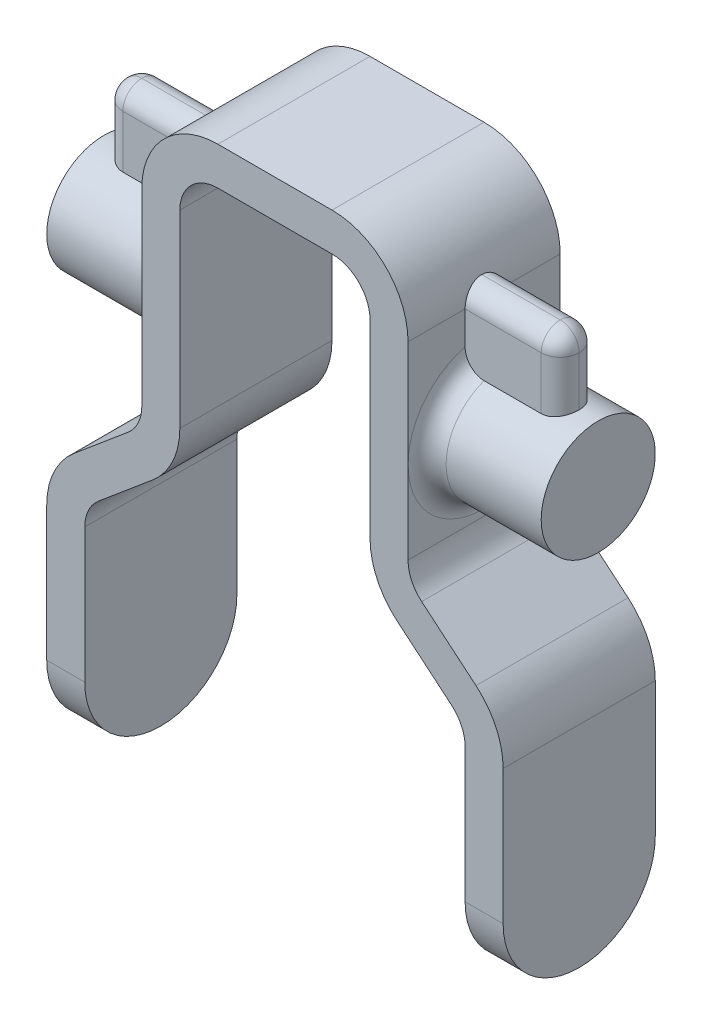
SolidWorks part; units mm, degrees
material "1.0570 (S355J2G3)"
ref_plane "Front Plane" through (0, 0, 0) normal (0, 0, 1) x (1, 0, 0)
ref_plane "Top Plane" through (0, 0, 0) normal (0, 1, 0) x (1, 0, 0)
ref_plane "Right Plane" through (0, 0, 0) normal (1, 0, 0) x (0, 0, -1)
sketch "Sketch1" plane through (0, 0, 0) normal (0, 0, 1) x (1, 0, 0)
  line L0 (0, 0) -> (12.5, 0)
  line L1 (12.5, 0) -> (12.5, -34.5113)
  line L2 (12.5, -34.5113) -> (25, -45)
  line L3 (25, -45) -> (25, -75)
  line L4 (25, -75) -> (30, -75)
  line L5 (30, -75) -> (30, -42.6685)
  line L6 (30, -42.6685) -> (17.5, -32.1797)
  line L7 (17.5, -32.1797) -> (17.5, 5)
  line L8 (17.5, 5) -> (0, 5)
  line L9 (0, 5) -> (0, 0)
  line L10 (0, -7.9824) -> (0, 6.9311) construction
  dimension "D1" = 25
  dimension "D2" = 60
  dimension "D3" = 5
  dimension "D4" = 130
  dimension "D5" = 30
  dimension "D6" = 80
  dimension "D7" = 5
  dimension "D8" = 5
  dimension "D9" = 5
extrude "Boss-Extrude1" add sketch "Sketch1" along normal blind 20 contours L8 L9 L0 L1 L2 L3 L4 L5 L6 L7
sketch "Sketch2" plane through (17.5, 0, 0) normal (1, 0, 0) x (0, 0, -1)
  line L0 (-20, -75) -> (0, -75) construction
  circle A0 centre (-10, -19) radius 7.5
  dimension "D1" = 15
  dimension "D2" = 56
extrude "Boss-Extrude2" add sketch "Sketch2" along normal offset from surface (15 mm away) 2.5 up to face at (30, -58.8342, 10) offset beyond the face yes
sketch "Sketch3" plane through (17.5, 0, 0) normal (1, 0, 0) x (0, 0, -1)
  line L0 (-7.5, -19) -> (-12.5, -19)
  line L1 (-12.5, -19) -> (-12.5, -2.5)
  line L2 (-12.5, -2.5) -> (-7.5, -2.5)
  line L3 (-10, -2.5) -> (-10, -19)
  line L4 (-10, -22.4781) -> (-10, 2.7287) construction
  line L5 (-7.5, -19) -> (-7.5, -2.5)
  dimension "D1" = 5
  dimension "D2" = 16.5
extrude "Boss-Extrude3" add sketch "Sketch3" along normal up to surface (12.5 mm away) contours L2 L5 L0 L1 up to face at (30, -58.8342, 10)
fillet "Fillet1" radius 2.5 5 edges at (30, -7.2145, 7.5) (30, -7.2145, 12.5) (23.75, -2.5, 7.5) (23.75, -2.5, 12.5) (17.5, -26.5, 10)
fillet "Fillet2" radius 5 3 edges at (25, -45, 10) (17.5, -32.1797, 10) (12.5, 0, 10)
fillet "Fillet3" radius 10 3 edges at (30, -42.6685, 10) (12.5, -34.5113, 10) (17.5, 5, 10)
fillet "Fillet4" radius 10 2 edges at (27.5, -75, 0) (27.5, -75, 20)
mirror "Mirror6" about plane through (0, 0, 0) normal (1, 0, 0) of "Boss-Extrude2", "Boss-Extrude1", "Fillet4", "Fillet3", "Fillet2", "Fillet1", "Boss-Extrude3"
